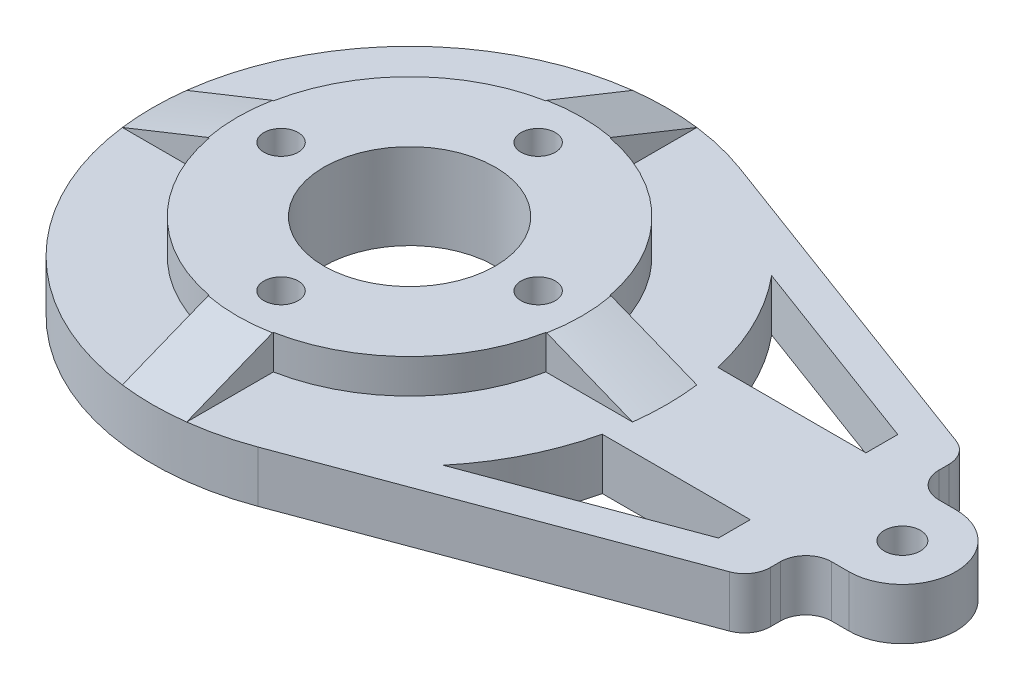
SolidWorks part; units mm, degrees
ref_plane "Front Plane" through (0, 0, 0) normal (0, 0, 1) x (1, 0, 0)
ref_plane "Top Plane" through (0, 0, 0) normal (0, 1, 0) x (1, 0, 0)
ref_plane "Right Plane" through (0, 0, 0) normal (1, 0, 0) x (0, 0, -1)
sketch "Sketch1" plane through (0, 0, 0) normal (0, 1, 0) x (1, 0, 0)
  circle A0 centre (0, 0) radius 20
  circle A1 centre (0, 0) radius 40
  dimension "D1" = 40
  dimension "D2" = 80
extrude "Boss-Extrude1" add sketch "Sketch1" along normal blind 8
sketch "Sketch3" plane through (0, 0, 0) normal (0, -1, 0) x (1, 0, 0)
  line L0 (20.8942, 56.2444) -> (105, 25)
  line L1 (105, 25) -> (105, -25)
  line L2 (105, -25) -> (20.8942, -56.2444)
  arc A0 (20.8942, 56.2444) -> (20.8942, -56.2444) centre (0, 0) ccw
  circle A2 centre (0, 0) radius 20
  circle A3 centre (0, 0) radius 20 construction
  point P6 (105, 0)
  dimension "D3" = 60
  dimension "D1" = 50
  dimension "D2" = 105
extrude "Boss-Extrude2" add sketch "Sketch3" along normal blind 12
sketch "Sketch5" plane through (0, -12, 0) normal (0, -1, 0) x (1, 0, 0)
  circle A0 centre (0, 30) radius 7.5
  circle A1 centre (30, 0) radius 7.5
  circle A2 centre (0, -30) radius 7.5
  circle A3 centre (-30, 0) radius 7.5
  point P12 (0, 0)
  dimension "D1" = 15
  dimension "D2" = 30
  dimension "D3" = 4
extrude "Cut-Extrude3" cut sketch "Sketch5" against normal blind 10
sketch "Sketch2" plane through (0, 8, 0) normal (0, 1, 0) x (1, 0, 0)
  circle A0 centre (30, 0) radius 4
  circle A1 centre (0, -30) radius 4
  circle A2 centre (-30, 0) radius 4
  circle A3 centre (0, 30) radius 4
  point P12 (0, 0)
  dimension "D1" = 8
  dimension "D2" = 30
  dimension "D3" = 4
extrude "Cut-Extrude1" cut sketch "Sketch2" against normal up to surface (20 mm away) up to face at (0, -12, 22.5)
sketch "Sketch6" plane through (0, 0, 0) normal (0, 1, 0) x (1, 0, 0)
  line L0 (-7.5, -39.2906) -> (-7.5, -59.5294)
  line L1 (7.5, -39.2906) -> (7.5, -59.5294)
  line L2 (-39.2906, -7.5) -> (-59.5294, -7.5)
  line L3 (-39.2906, 7.5) -> (-59.5294, 7.5)
  line L4 (-7.5, 39.2906) -> (-7.5, 59.5294)
  line L5 (7.5, 39.2906) -> (7.5, 59.5294)
  line L6 (39.2906, 7.5) -> (59.5294, 7.5)
  line L7 (39.2906, -7.5) -> (59.5294, -7.5)
  arc A0 (-7.5, -39.2906) -> (7.5, -39.2906) centre (0, 0) ccw
  circle A1 centre (0, 0) radius 40 construction
  arc A2 (-7.5, -59.5294) -> (7.5, -59.5294) centre (0, 0) ccw
  arc A3 (20.8942, 56.2444) -> (20.8942, -56.2444) centre (0, 0) ccw construction
  arc A4 (-59.5294, 7.5) -> (-59.5294, -7.5) centre (0, 0) ccw
  arc A5 (-39.2906, 7.5) -> (-39.2906, -7.5) centre (0, 0) ccw
  arc A6 (7.5, 59.5294) -> (-7.5, 59.5294) centre (0, 0) ccw
  arc A7 (7.5, 39.2906) -> (-7.5, 39.2906) centre (0, 0) ccw
  arc A8 (59.5294, -7.5) -> (59.5294, 7.5) centre (0, 0) ccw
  arc A9 (39.2906, -7.5) -> (39.2906, 7.5) centre (0, 0) ccw
  point P11 (0, -60)
  point P12 (0, -40)
  point P28 (0, 0)
  dimension "D1" = 15
  dimension "D2" = 4
extrude "Boss-Extrude3" add sketch "Sketch6" along normal up to surface (8 mm away) up to face at (30, 8, 4)
chamfer "Chamfer1" distance 8 angle 68 4 edges at (0, 8, -60) (60, 8, 0) (0, 8, 60) (-60, 8, 0) first distance on face at (-15.8462, 1.5, 0) first distance on face at (59.7647, 4, 0)
sketch "Sketch7" plane through (0, -12, 0) normal (0, -1, 0) x (1, 0, 0)
  line L2 (115, 12.5) -> (105, 12.5)
  line L3 (105, -25) -> (105, 25) construction
  line L4 (105, 12.5) -> (105, -12.5)
  line L5 (105, -12.5) -> (115, -12.5)
  arc A0 (115, 12.5) -> (115, -12.5) centre (115, 0) cw
  point P3 (105, 0)
  point P5 (105, 0)
  dimension "D1" = 25
  dimension "D2" = 10
extrude "Boss-Extrude4" add sketch "Sketch7" against normal up to surface (12 mm away) up to face at (40.8222, 0, 0)
fillet "Fillet1" radius 6 4 edges at (105, -6, 25) (105, -6, -25) (105, -6, -12.5) (105, -6, 12.5)
sketch "Sketch8" plane through (0, -12, 0) normal (0, -1, 0) x (1, 0, 0)
  line L1 (111.2472, -6.5) -> (118.7528, -6.5)
  line L2 (118.7528, -6.5) -> (122.5056, 0)
  line L3 (122.5056, 0) -> (118.7528, 6.5)
  line L4 (118.7528, 6.5) -> (111.2472, 6.5)
  line L5 (111.2472, 6.5) -> (107.4944, 0)
  line L6 (107.4944, 0) -> (111.2472, -6.5)
  circle A0 centre (115, 0) radius 6.5 construction
  arc A1 (115, -12.5) -> (115, 12.5) centre (115, 0) ccw construction
  point P13 (127.5, 0)
  dimension "D1" = 13
extrude "Cut-Extrude4" cut sketch "Sketch8" against normal blind 6
sketch "Sketch9" plane through (0, -6, 0) normal (0, -1, 0) x (1, 0, 0)
  circle A0 centre (115, 0) radius 4.2
  dimension "D1" = 8.4
extrude "Cut-Extrude5" cut sketch "Sketch9" against normal up to surface (6 mm away) up to face at (-31.9052, 0, -31.9052)
sketch "Sketch11" plane through (0, 0, 0) normal (0, 1, 0) x (1, 0, 0)
  line L1 (93, 20.9237) -> (93, 13.5)
  line L2 (93, 13.5) -> (58.4615, 13.5)
  line L5 (46.1679, 38.3213) -> (93, 20.9237)
  line L6 (20.8942, 56.2444) -> (101.0894, 26.4527) construction
  line L8 (59.5294, 7.5) -> (39.2906, 7.5) construction
  line L9 (105, 20.8283) -> (105, 18.5) construction
  arc A0 (58.4615, 13.5) -> (46.1679, 38.3213) centre (0, 0) ccw
  point P8 (46.1679, 38.3213)
  point P9 (46.2632, 38.2859)
  point P10 (47.4516, 36.7199)
  dimension "D1" = 60
  dimension "D2" = 8
  dimension "D4" = 6
  dimension "D5" = 12
extrude "Cut-Extrude7" cut sketch "Sketch11" against normal up to surface (12 mm away) up to face at (115, -12, 0)
mirror "Mirror1" about plane through (0, 0, 0) normal (0, 0, 1) of "Cut-Extrude7"
